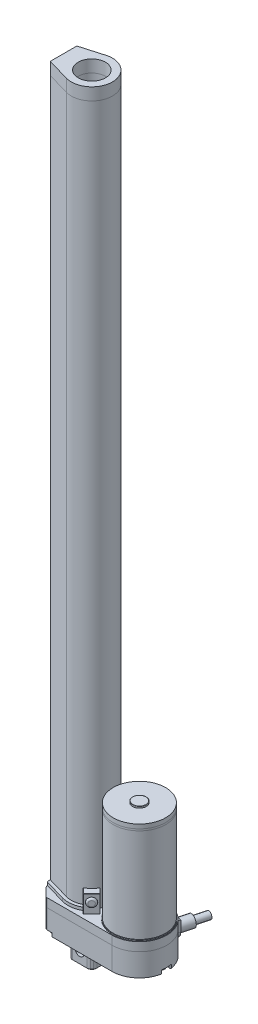
SolidWorks part; units mm, degrees
note: The reader was unsure of these and kept them because the rebuilt part matched: shared geometry of "Sketch1<3>", "Sketch41<11>", "Sketch41<12>", "Sketch45<3>".
ref_plane "Front Plane" through (0, 0, 0) normal (0, 0, 1) x (1, 0, 0)
ref_plane "Top Plane" through (0, 0, 0) normal (0, 1, 0) x (1, 0, 0)
ref_plane "Right Plane" through (0, 0, 0) normal (1, 0, 0) x (0, 0, -1)
sketch "Sketch1" plane through (0, 0, 0) normal (0, 1, 0) x (1, 0, 0)
  line L0 (0, 32.639) -> (7.239, 39.878)
  line L1 (7.239, 0) -> (55.118, 0)
  line L2 (0, 7.239) -> (0, 32.639)
  line L3 (7.239, 39.878) -> (55.118, 39.878)
  line L4 (7.239, 0) -> (0, 7.239)
  arc A0 (55.118, 0) -> (55.118, 39.878) centre (55.118, 19.939) ccw
  point P0 (0, 0)
  point P2 (0, 39.878)
  dimension "D1" = 55.118
  dimension "D2" = 39.878
extrude "Boss-Extrude1" add sketch "Sketch1" along normal blind 6.35
sketch "Sketch6" plane through (0, 6.35, 0) normal (0, 1, 0) x (1, 0, 0)
  circle A0 centre (55.118, 19.939) radius 19.431
extrude "Boss-Extrude4" add sketch "Sketch6" along normal blind 0.762 separate body contours A0
sketch "Sketch7" plane through (0, 7.112, 0) normal (0, 1, 0) x (1, 0, 0)
  circle A0 centre (55.118, 19.939) radius 19.05
  dimension "D1" = 38.1
extrude "Boss-Extrude5" add sketch "Sketch7" along normal blind 68.326 separate body
sketch "Sketch8" plane through (0, 75.438, 0) normal (0, 1, 0) x (1, 0, 0)
  circle A0 centre (55.118, 19.939) radius 4.953
  dimension "D1" = 9.906
fillet "Fillet6" radius 5.08 2 edges at (0, 3.175, -7.239) (0, 3.175, -32.639)
fillet "Fillet7" radius 1.905 2 edges at (7.239, 3.175, -39.878) (7.239, 3.175, 0)
sketch "Sketch15" plane through (0, 6.35, 0) normal (0, 1, 0) x (1, 0, 0)
  line L0 (35.5603, 29.0153) -> (35.5603, 29.0265)
  line L2 (0, 30.5348) -> (0, 9.3432) construction
  line L3 (0, 19.939) -> (0, 10.2869)
  line L4 (0, 19.939) -> (0, 29.591)
  line L5 (0, 10.2869) -> (16.412, 5.5423)
  line L7 (35.5603, 10.8628) -> (35.5603, 10.8515)
  line L10 (0, 29.591) -> (16.4119, 34.3357)
  arc A0 (16.412, 5.5423) -> (16.4119, 34.3357) centre (20.574, 19.939) ccw
ref_plane "Plane4" through (13.8375, 0, -51.6424) normal (0.2588, 0, -0.9659) x (0, -1, 0)
ref_plane "Plane5" through (12.5227, 0, -46.7355) normal (0.2588, 0, -0.9659) x (0, -1, 0)
sketch "Sketch23" plane through (12.5227, 0, -46.7355) normal (0.2588, 0, -0.9659) x (0, -1, 0)
  line L0 (-6.35, -67.5103) -> (-6.35, -28.6483) construction
  line L1 (-2.032, -53.8839) -> (5.588, -53.8839)
  line L2 (-2.032, -53.8839) -> (-2.032, -42.4539)
  line L3 (-2.032, -42.4539) -> (5.588, -42.4539)
  arc A0 (5.588, -53.8839) -> (5.588, -42.4539) centre (5.588, -48.1689) ccw
  dimension "D1" = 11.43
  dimension "D2" = 7.62
  dimension "D3" = 4.318
extrude "Boss-Extrude15" add sketch "Sketch23" along normal blind 6.35
sketch "Sketch24" plane through (14.1662, 0, -52.8692) normal (0.2588, 0, -0.9659) x (-0.9659, 0, -0.2588)
  circle A0 centre (-48.1689, -5.588) radius 4.064
  dimension "D1" = 8.128
extrude "Boss-Extrude16" add sketch "Sketch24" along normal blind 10.16
sketch "Sketch25" plane through (16.7959, 0, -62.683) normal (0.2588, 0, -0.9659) x (-0.9659, 0, -0.2588)
  circle A0 centre (-48.1689, -5.588) radius 2.54
  dimension "D1" = 5.08
extrude "Boss-Extrude17" add sketch "Sketch25" along normal blind 10.16
extrude "Boss-Extrude19" add sketch "Sketch1<3>" against normal blind 16.51 separate body
sketch "Sketch1<3>" plane through (0, 0, 0) normal (0, 1, 0) x (1, 0, 0) same geometry as "Sketch1"
fillet "Fillet13" radius 1.905 2 edges at (7.239, -8.255, 0) (7.239, -8.255, -39.878)
fillet "Fillet14" radius 5.08 2 edges at (0, -8.255, -32.639) (0, -8.255, -7.239)
sketch "Sketch26" plane through (0, -16.51, 0) normal (0, -1, 0) x (-1, 0, 0)
  line L4 (-20.574, 28.829) -> (-11.684, 28.829)
  line L5 (-20.574, 28.829) -> (-29.464, 28.829)
  line L6 (-11.684, 28.829) -> (-11.684, 11.049)
  line L7 (-11.684, 11.049) -> (-29.464, 11.049)
  line L8 (-29.464, 11.049) -> (-29.464, 28.829)
extrude "Boss-Extrude20" add sketch "Sketch26" along normal blind 18.796 separate body
chamfer "Chamfer1" distance 2.54 angle 45 4 edges at (29.464, -25.908, -28.829) (29.464, -25.908, -11.049) (11.684, -25.908, -11.049) (11.684, -25.908, -28.829)
fillet "Fillet15" radius 2.54 8 edges at (11.684, -25.908, -13.589) (14.224, -25.908, -11.049) (26.924, -25.908, -11.049) (29.464, -25.908, -13.589) (29.464, -25.908, -26.289) (26.924, -25.908, -28.829) (11.684, -25.908, -26.289) (14.224, -25.908, -28.829)
chamfer "Chamfer2" distance 0.762 angle 45 16 edges at (14.3041, -35.306, -11.2423) (20.574, -35.306, -11.049) (26.8439, -35.306, -11.2423) (28.194, -35.306, -12.319) (29.2707, -35.306, -13.6691) (29.464, -35.306, -19.939) (29.2707, -35.306, -26.2089) (28.194, -35.306, -27.559) (26.8439, -35.306, -28.6357) (20.574, -35.306, -28.829) (14.3041, -35.306, -28.6357) (12.954, -35.306, -27.559) (11.8773, -35.306, -26.2089) (11.684, -35.306, -19.939) (11.8773, -35.306, -13.6691) (12.954, -35.306, -12.319)
sketch "Sketch27" plane through (0, 0, -11.049) normal (0, 0, 1) x (1, 0, 0)
  line L0 (25.8719, -35.306) -> (15.2761, -35.306) construction
  circle A0 centre (20.574, -26.67) radius 3.175
  point P5 (20.574, -35.306)
  dimension "D1" = 8.636
  dimension "D2" = 6.35
extrude "Cut-Extrude3" cut sketch "Sketch27" against normal blind 19.05
sketch "Sketch28" plane through (0, 75.438, 0) normal (0, 1, 0) x (1, 0, 0)
  circle A0 centre (55.118, 19.939) radius 19.05
extrude "Boss-Extrude22" add sketch "Sketch28" along normal blind 1.27 separate body
sketch "Sketch29" plane through (0, 76.708, 0) normal (0, 1, 0) x (1, 0, 0)
  circle A0 centre (55.118, 19.939) radius 19.05
extrude "Boss-Extrude24" add sketch "Sketch29" along normal blind 3.048 separate body contours A0
extrude "Boss-Extrude25" add sketch "Sketch8" along normal blind 1.27 from surface at 4.318 contours A0 starting at face at (55.118, 79.756, -0.889)
fillet "Fillet16" radius 0.2286 1 edges at (55.118, 81.026, -14.986)
extrude "Boss-Extrude26" add sketch "Sketch15" along normal blind 508.381 separate body contours L5 A0 L10 L4 L3
sketch "Sketch32" plane through (0, 514.731, 0) normal (0, 1, 0) x (1, 0, 0)
  line L0 (0, 10.2869) -> (0, 29.591)
  line L1 (0, 29.591) -> (16.4119, 34.3357)
  line L2 (0, 10.2869) -> (16.412, 5.5423)
  arc A0 (16.412, 5.5423) -> (16.4119, 34.3357) centre (20.574, 19.939) ccw
extrude "Boss-Extrude27" add sketch "Sketch32" along normal blind 8.89 separate body
sketch "Sketch33" plane through (0, 523.621, 0) normal (0, 1, 0) x (1, 0, 0)
  circle A0 centre (20.574, 19.939) radius 9.906
  dimension "D1" = 19.812
sketch3d "3DSketch1" plane through (0, 0, 0) normal (0, 0, 1) x (1, 0, 0)
sketch "Sketch41" plane through (0, 6.35, 0) normal (0, 1, 0) x (1, 0, 0)
  line L0 (16.4119, 34.3357) -> (0, 29.591)
  line L1 (37.5429, 9.0662) -> (33.7712, 12.8379)
  line L2 (0.2737, 32.0497) -> (15.777, 36.5318)
  line L3 (37.5429, 9.0662) -> (31.2567, 2.78)
  line L4 (0, 29.591) -> (0, 30.5348)
  line L5 (0, 30.5348) -> (0.2737, 32.0497)
  line L6 (-0.6349, 31.7871) -> (15.777, 36.5318) construction
  line L7 (0, 19.9389) -> (7.9017, 19.9389)
  line L8 (31.2567, 2.78) -> (27.426, 6.6107)
  line L9 (0, 10.2869) -> (0, 29.591) construction
  line L10 (0, 10.2869) -> (0, 9.3431)
  line L12 (37.5429, 30.8116) -> (33.7712, 27.0399)
  line L13 (37.5429, 30.8116) -> (31.2567, 37.0978)
  line L14 (31.2567, 37.0978) -> (27.426, 33.2671)
  line L15 (0, 9.3431) -> (0.2737, 7.8281)
  line L16 (0.2737, 7.8281) -> (15.777, 3.3461)
  line L17 (16.4119, 5.5422) -> (0, 10.2869)
  line L18 (-0.6349, 8.0908) -> (15.7771, 3.3462) construction
  line L19 (27.426, 33.2671) -> (29.1122, 34.9533)
  line L20 (0, 29.591) -> (16.4119, 34.3357) construction
  line L21 (0, 10.2869) -> (16.412, 5.5423) construction
  arc A0 (16.4119, 34.3357) -> (33.7712, 27.0399) centre (20.574, 19.939) cw
  arc A1 (15.777, 36.5318) -> (29.1122, 34.9533) centre (20.574, 19.939) cw
  arc A2 (16.4119, 34.3357) -> (16.412, 5.5423) centre (20.574, 19.939) cw construction
  arc A3 (15.777, 36.5318) -> (15.7771, 3.3462) centre (20.574, 19.939) cw construction
  arc A4 (16.4119, 34.3357) -> (27.426, 33.2671) centre (20.574, 19.939) cw
  arc A5 (15.777, 3.3461) -> (29.1122, 4.9245) centre (20.574, 19.9389) ccw
  arc A6 (16.4119, 5.5422) -> (33.7712, 12.8379) centre (20.574, 19.9389) ccw
  line M5 (0, 30.5348) -> (0, 9.3432)
  arc M6 (0, 9.3432) -> (1.4879, 5.7511) centre (5.08, 9.3432) ccw
extrude "Boss-Extrude30" add sketch "Sketch41" along normal blind 2.159 separate body contours A1 L2 L5 L0 A0 L14 M5
extrude "Boss-Extrude31" add sketch "Sketch41<11>" along normal blind 2.159 separate body contours A6 L17 L15 L16 A5 L8 M5 M6
sketch "Sketch41<11>" plane through (0, 6.35, 0) normal (0, 1, 0) x (1, 0, 0) same geometry as "Sketch41"
extrude "Boss-Extrude33" add sketch "Sketch41<12>" along normal blind 12.7 separate body contours L14 A0 L12 L13 | A6 L8 L3 L1
sketch "Sketch41<12>" plane through (0, 6.35, 0) normal (0, 1, 0) x (1, 0, 0) same geometry as "Sketch41"
fillet "Fillet17" radius 0.2286 5 edges at (35.657, 19.05, -28.9258) (29.3413, 19.05, -35.1825) (34.3998, 19.05, -33.9547) (37.5429, 12.7, -30.8116) (31.2567, 12.7, -37.0978)
fillet "Fillet18" radius 0.2286 5 edges at (35.657, 19.05, -10.9521) (29.3413, 19.05, -4.6954) (37.5429, 12.7, -9.0662) (34.3998, 19.05, -5.9231) (31.2567, 12.7, -2.78)
sketch "Sketch43" plane through (34.1773, 0, -34.1773) normal (0.7071, 0, -0.7071) x (-0.7071, 0, -0.7071)
  circle A0 centre (-0.3147, 13.7414) radius 3.175
extrude "Boss-Extrude34" add sketch "Sketch43" along normal blind 1.27 separate body
fillet "Fillet19" radius 1.27 1 edges at (33.0527, 13.7414, -37.0978)
sketch "Sketch44" plane through (14.2383, 0, 14.2383) normal (0.7071, 0, 0.7071) x (0.7071, 0, -0.7071)
  circle A0 centre (28.5126, 13.7414) radius 3.175
extrude "Boss-Extrude35" add sketch "Sketch44" along normal blind 1.27 separate body
fillet "Fillet20" radius 1.27 1 edges at (37.5429, 13.7414, -7.2702)
sketch "Sketch45" plane through (0, -16.51, 0) normal (0, -1, 0) x (1, 0, 0)
  line L0 (4.0845, -36.7235) -> (6.681, -39.32)
  line L2 (6.681, -39.32) -> (1.4879, -34.1269) construction
  line L4 (55.118, -39.878) -> (8.0281, -39.878) construction
  line L5 (11.3938, -39.878) -> (8.0281, -39.878)
  line L6 (11.3938, 0) -> (8.0281, 0)
  line L7 (4.0845, -3.1545) -> (6.681, -0.558)
  arc A0 (11.2821, -38.9146) -> (11.3938, -39.878) centre (11.8197, -39.3405) ccw
  arc A1 (11.2821, -38.9146) -> (5.0443, -35.9783) centre (8.8543, -35.9783) ccw
  arc A2 (11.2821, -0.9634) -> (11.3938, 0) centre (11.8197, -0.5375) cw
  arc A3 (5.0443, -35.9783) -> (4.0845, -36.7235) centre (4.1918, -35.871) cw
  arc A4 (5.0443, -3.8997) -> (4.0845, -3.1545) centre (4.1918, -4.007) ccw
  arc A5 (11.2821, -0.9634) -> (5.0443, -3.8997) centre (8.8543, -3.8997) cw
  arc A6 (55.118, -39.878) -> (55.118, 0) centre (55.118, -19.939) ccw construction
  arc A7 (73.6621, -16.9922) -> (73.6621, -22.8858) centre (71.247, -19.939) ccw
  arc A8 (73.6621, -22.8858) -> (74.7121, -23.6317) centre (73.8141, -23.7837) cw
  arc A9 (73.6621, -16.9922) -> (74.7121, -16.2463) centre (73.8141, -16.0943) ccw
  arc A10 (8.0281, -39.878) -> (6.681, -39.32) centre (8.0281, -37.973) cw
  arc A11 (8.0281, 0) -> (6.681, -0.558) centre (8.0281, -1.905) ccw
  arc A12 (74.7121, -23.6317) -> (74.7121, -16.2463) centre (55.118, -19.939) ccw
  line M8 (1.4879, -34.1269) -> (6.681, -39.32)
  arc M9 (6.681, -39.32) -> (8.0281, -39.878) centre (8.0281, -37.973) ccw
  line M10 (8.0281, -39.878) -> (55.118, -39.878)
  line M12 (55.118, 0) -> (8.0281, 0)
  arc M13 (8.0281, 0) -> (6.681, -0.558) centre (8.0281, -1.905) ccw
  line M14 (6.681, -0.558) -> (1.4879, -5.7511)
extrude "Cut-Extrude5" cut sketch "Sketch45" against normal blind 2.54 contours A1 A3 A0 M8 M9 M10 | A5 A2 A4 M12 M13 M14
extrude "Cut-Extrude6" cut sketch "Sketch45<3>" against normal blind 2.54
sketch "Sketch45<3>" plane through (0, -16.51, 0) normal (0, -1, 0) x (1, 0, 0) same geometry as "Sketch45"
sketch "Sketch47" plane through (0, -13.97, 0) normal (0, -1, 0) x (-1, 0, 0)
  circle A0 centre (-8.8543, 35.9783) radius 2.54
  circle A1 centre (-8.8543, 3.8997) radius 2.54
  circle A2 centre (-71.247, 19.939) radius 2.54
extrude "Boss-Extrude36" add sketch "Sketch47" along normal blind 2.54 separate body
fillet "Fillet22" radius 1.524 1 edges at (8.8543, -16.51, -38.5183)
fillet "Fillet23" radius 1.524 1 edges at (8.8543, -16.51, -6.4397)
sketch "Sketch48" plane through (0, 0, 0) normal (-1, 0, 0) x (0, 0, 1)
  circle A0 centre (-19.939, 12.7) radius 3.81
extrude "Boss-Extrude37" add sketch "Sketch48" along normal blind 1.524
fillet "Fillet24" radius 1.524 1 edges at (-1.524, 12.7, -16.129)
fillet "Fillet25" radius 1.524 1 edges at (71.247, -16.51, -22.479)
sketch "Sketch49" plane through (0, 0, 0) normal (-1, 0, 0) x (0, 0, 1)
  line L0 (-19.9389, 514.731) -> (-19.9389, 509.778) construction
  line L1 (-29.591, 514.731) -> (-10.2869, 514.731) construction
  line L2 (-30.5348, 6.35) -> (-9.3432, 6.35) construction
  circle A0 centre (-19.9389, 509.778) radius 3.81
  dimension "Flat Head Screw" = 503.428
extrude "Cut-Extrude7" cut sketch "Sketch49" against normal blind 2.54
sketch "Sketch50" plane through (2.54, 0, 0) normal (-1, 0, 0) x (0, 0, 1)
  circle A0 centre (-19.9389, 509.778) radius 3.556
extrude "Boss-Extrude39" add sketch "Sketch50" along normal blind 2.54 contours A0
extrude "Cut-Extrude12" cut sketch "Sketch33" against normal blind 518.16
equation "\"Stroke\"= 18"
equation "\"D1@Boss-Extrude26\"= \"Stroke\" + 2.015"
equation "\"Flat Head Screw@Sketch49\"= \"Stroke\" + 1.82"
equation "\"Hole to Hole@Sketch52\"= \"Stroke\" + 4.13"
